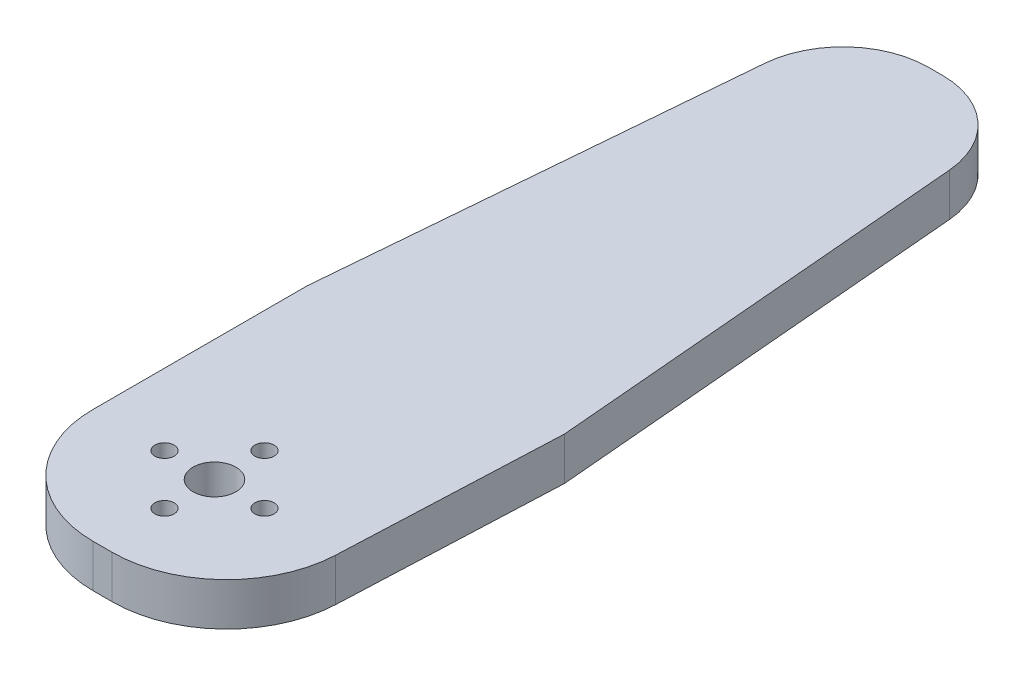
SolidWorks part; units mm, degrees
ref_plane "Front Plane" through (0, 0, 0) normal (0, 0, 1) x (1, 0, 0)
ref_plane "Top Plane" through (0, 0, 0) normal (0, 1, 0) x (1, 0, 0)
ref_plane "Right Plane" through (0, 0, 0) normal (1, 0, 0) x (0, 0, -1)
ref_plane "PY_m6_000" through (0, -6, 0) normal (0, 1, 0) x (1, 0, 0)
sketch "S_prism1" plane through (0, -6, 0) normal (0, 1, 0) x (1, 0, 0)
  line L0 (-1, -16) -> (1.6805, -16)
  line L1 (17.6654, -0.695) -> (19, 30)
  line L2 (19, 30) -> (13.9407, 89.0248)
  line L3 (1.9846, 100) -> (0.0154, 100)
  line L4 (-11.9407, 89.0248) -> (-17, 30)
  line L5 (-17, 30) -> (-17, 0)
  arc A0 (-17, 0) -> (-1, -16) centre (-1, 0) ccw
  arc A1 (1.6805, -16) -> (17.6654, -0.695) centre (1.6805, 0) ccw
  arc A2 (13.9407, 89.0248) -> (1.9846, 100) centre (1.9846, 88) ccw
  arc A3 (0.0154, 100) -> (-11.9407, 89.0248) centre (0.0154, 88) ccw
extrude "Boss_1" add sketch "S_prism1" along normal blind 6
ref_plane "PY_m8_000" through (0, -8, 0) normal (0, 1, 0) x (1, 0, 0)
sketch "S_cyl2" plane through (0, -8, 0) normal (0, 1, 0) x (1, 0, 0)
  circle A0 centre (0, 0) radius 12.5
  dimension "D1_S_cyl2" = 25
extrude "Boss_2" add sketch "S_cyl2" along normal blind 2
ref_plane "PY_m8_100" through (0, -8.1, 0) normal (0, 1, 0) x (1, 0, 0)
sketch "S_hole3" plane through (0, -8.1, 0) normal (0, 1, 0) x (1, 0, 0)
  circle A0 centre (0, 0) radius 3
  dimension "D1_S_hole3" = 6
extrude "Hole_3" cut sketch "S_hole3" along normal blind 8.2
sketch "S_hole4" plane through (0, -8.1, 0) normal (0, 1, 0) x (1, 0, 0)
  circle A0 centre (7, 0) radius 1.35
  dimension "D1_S_hole4" = 2.7
  dimension "P2" = 7
extrude "Hole_4" cut sketch "S_hole4" along normal blind 8.2
sketch "S_hole5" plane through (0, -8.1, 0) normal (0, 1, 0) x (1, 0, 0)
  circle A0 centre (0, -7) radius 1.35
  dimension "D1_S_hole5" = 2.7
  dimension "P2" = 7
extrude "Hole_5" cut sketch "S_hole5" along normal blind 8.2
sketch "S_hole6" plane through (0, -8.1, 0) normal (0, 1, 0) x (1, 0, 0)
  circle A0 centre (-7, 0) radius 1.35
  dimension "D1_S_hole6" = 2.7
  dimension "P2" = 7
extrude "Hole_6" cut sketch "S_hole6" along normal blind 8.2
sketch "S_hole7" plane through (0, -8.1, 0) normal (0, 1, 0) x (1, 0, 0)
  circle A0 centre (0, 7) radius 1.35
  dimension "D1_S_hole7" = 2.7
  dimension "P2" = 7
extrude "Hole_7" cut sketch "S_hole7" along normal blind 8.2
equation "\"plate_t\" = 3"
equation "\"clearance\" = 0.4"
